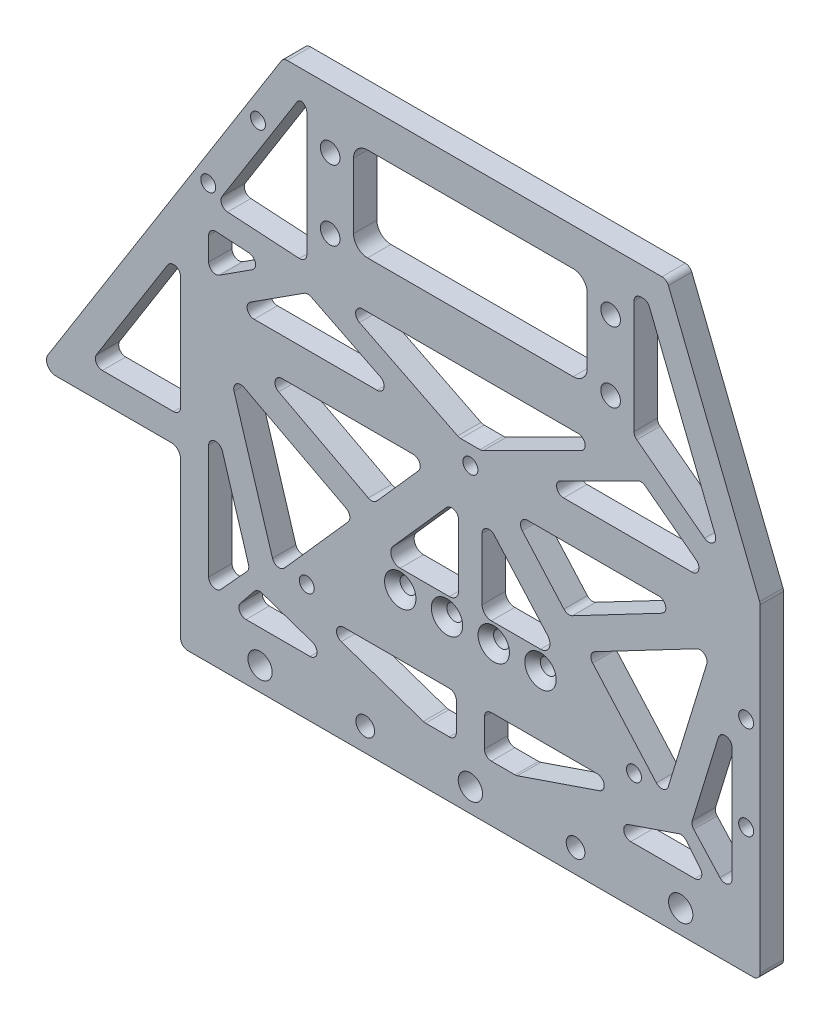
SolidWorks part; units mm, degrees
material "Thornel Mat VMA"
ref_plane "前视基准面" through (0, 0, 0) normal (0, 0, 1) x (1, 0, 0)
ref_plane "上视基准面" through (0, 0, 0) normal (0, 1, 0) x (1, 0, 0)
ref_plane "右视基准面" through (0, 0, 0) normal (1, 0, 0) x (0, 0, -1)
sketch "草图1" plane through (0, 0, 0) normal (0, 0, 1) x (1, 0, 0)
  line L1 (-62, 60) -> (62, 60)
  line L2 (-62, 60) -> (-62, -60)
  line L3 (-62, -60) -> (62, -60)
  line L4 (62, 60) -> (62, -60)
  line L5 (-62, 60) -> (62, -60) construction
  line L6 (-62, -60) -> (62, 60) construction
  point P0 (0, 0)
  dimension "D1" = 124
  dimension "D2" = 120
extrude "凸台-拉伸1" add sketch "草图1" along normal blind 5
sketch "草图2" plane through (0, 0, 5) normal (0, 0, 1) x (1, 0, 0)
  line L0 (-35, -35) -> (35, -35) construction
  line L1 (-62, -60) -> (62, -60) construction
  circle A0 centre (-35, -35) radius 1.6
  circle A1 centre (35, -35) radius 1.6
  point P2 (0, -35)
  dimension "D3" = 3.2
  dimension "D1" = 70
  dimension "D2" = 25
extrude "切除-拉伸1" cut sketch "草图2" against normal through all
sketch "草图3" plane through (0, 0, 5) normal (0, 0, 1) x (1, 0, 0)
  circle A0 centre (0, 4.5) radius 1.6
  circle A1 centre (35, -35) radius 1.6 construction
  dimension "D1" = 3.2
  dimension "D2" = 39.5
extrude "切除-拉伸2" cut sketch "草图3" against normal through all
sketch "草图4" plane through (0, 0, 5) normal (0, 0, 1) x (1, 0, 0)
  line L1 (-30, 47.5) -> (30, 47.5) construction
  line L2 (-30, 47.5) -> (-30, 32.5) construction
  line L3 (-30, 32.5) -> (30, 32.5) construction
  line L4 (30, 47.5) -> (30, 32.5) construction
  line L5 (-30, 47.5) -> (30, 32.5) construction
  line L6 (-30, 32.5) -> (30, 47.5) construction
  circle A0 centre (-30, 47.5) radius 2.1
  circle A1 centre (30, 32.5) radius 2.1
  circle A2 centre (30, 47.5) radius 2.1
  circle A3 centre (-30, 32.5) radius 2.1
  point P0 (0, 40)
  dimension "D4" = 4.2
  dimension "D1" = 40
  dimension "D2" = 15
  dimension "D3" = 60
extrude "切除-拉伸3" cut sketch "草图4" against normal through all
chamfer "倒角1" distance 22 distance2 35 1 edges at (-62, 60, 2.5) first distance on face at (0, 60, 2.5)
chamfer "倒角2" distance 50 distance2 20 1 edges at (62, 60, 2.5) first distance on face at (62, 0, 2.5)
sketch "草图7" plane through (0, 0, 5) normal (0, 0, 1) x (1, 0, 0)
  line L0 (-45, -55) -> (45, -55) construction
  line L1 (-62, -60) -> (62, -60) construction
  circle A0 centre (-45, -55) radius 2.6
  circle A1 centre (0, -55) radius 2.6
  circle A2 centre (45, -55) radius 2.6
  point P4 (0, -55)
  dimension "D3" = 5.2
  dimension "D1" = 5
  dimension "D2" = 90
extrude "切除-拉伸4" cut sketch "草图7" against normal through all
sketch "草图8" plane through (0, 0, 0) normal (0, 0, -1) x (-1, 0, 0)
  circle A0 centre (-59, -33) radius 1.6
  circle A1 centre (-59, -13) radius 1.6
  circle A2 centre (45.4427, 45.7039) radius 1.6
  circle A3 centre (56.0861, 28.7712) radius 1.6
  circle A4 centre (30, 47.5) radius 2.1 construction
  dimension "D1" = 3.2
  dimension "D2" = 45.4427
  dimension "D3" = 56.0861
  dimension "D4" = 59
  dimension "D5" = 28.7712
  dimension "D6" = 45.7039
  dimension "D7" = 13
  dimension "D8" = 33
extrude "切除-拉伸5" cut sketch "草图8" against normal through all
sketch "草图9" plane through (0, 0, 5) normal (0, 0, 1) x (1, 0, 0)
  line L6 (0, 4.5) -> (-35, -35)
  line L7 (25, 52) -> (-25, 52)
  line L8 (25, 52) -> (25, 32)
  line L9 (25, 32) -> (-25, 32)
  line L10 (-25, 52) -> (-25, 32)
  line L11 (25, 52) -> (-25, 32) construction
  line L12 (56, -54) -> (56, 8.8445)
  line L13 (56, 8.8445) -> (37.9378, 54)
  line L14 (37.9378, 54) -> (-36.6846, 54)
  line L15 (-36.6846, 54) -> (-56, 23.2709)
  line L16 (-56, 23.2709) -> (-56, -54)
  line L17 (-56, -54) -> (56, -54)
  line L18 (56, -54) -> (56, 8.8445)
  line L19 (56, 8.8445) -> (37.9378, 54)
  line L20 (37.9378, 54) -> (-36.6846, 54)
  line L21 (-36.6846, 54) -> (-56, 23.2709)
  line L22 (-56, 23.2709) -> (-56, -54)
  line L23 (-56, -54) -> (56, -54)
  line L24 (25, 32) -> (-25, 52) construction
  line L25 (-35, -35) -> (35, -35)
  line L26 (35, -35) -> (0, 4.5)
  line L27 (43.8887, -39) -> (1.8, 8.5)
  line L28 (-1.8, 8.5) -> (-43.8887, -39)
  line L29 (-43.8887, -39) -> (43.8887, -39)
  line L30 (28.3335, -32) -> (0, -0.0236)
  line L31 (0, -0.0236) -> (-28.3335, -32)
  line L32 (-28.3335, -32) -> (28.3335, -32)
  line L33 (56, 4.5) -> (-56, 4.5)
  line L34 (56, 8.5) -> (-56, 8.5)
  line L35 (56, 0.5) -> (-56, 0.5)
  line L36 (43.8887, -39) -> (56, 0.5)
  line L37 (43.8887, -39) -> (56, -54)
  line L38 (-56, 0.5) -> (-43.8887, -39)
  line L39 (-56, -54) -> (-43.8887, -39)
  line L40 (-58.8682, -0.3794) -> (-47.2241, -38.3555)
  line L41 (47.2241, -38.3555) -> (56, -48)
  line L42 (-47.2241, -38.3555) -> (-56, -48)
  line L43 (47.2241, -38.3555) -> (58.8682, -0.3794)
  line L44 (-53.1318, 1.3794) -> (-40.5532, -39.6445)
  line L45 (36.118, 19.7639) -> (39.1448, 21.2773)
  line L46 (-52.8621, 0.5) -> (-22.8444, -15.25)
  line L47 (40.5532, -39.6445) -> (53.1318, 1.3794)
  line L48 (35, 22) -> (-35, 22)
  line L49 (-35, 62) -> (-35, 22)
  line L50 (35, 62) -> (-35, 62)
  line L51 (35, 62) -> (35, 22)
  line L52 (25, 32) -> (56, 8.5)
  line L53 (-35, 22) -> (-56, 23.2709)
  line L54 (-35, 22) -> (-56, 8.5)
  line L55 (-27.2138, 24.0334) -> (-54.6481, 6.3971)
  line L56 (-27.2138, 24.0334) -> (-55.849, 25.7663)
  line L57 (-42.7862, 19.9666) -> (-57.3519, 10.6029)
  line L58 (-42.7862, 19.9666) -> (-56.151, 20.7755)
  line L59 (35, 22) -> (0, 4.5)
  line L60 (-35, 22) -> (0, 4.5)
  line L61 (23.4897, 30.0077) -> (54.4897, 6.5077)
  line L62 (33.882, 24.2361) -> (0, 7.2951)
  line L63 (-33.882, 24.2361) -> (0, 7.2951)
  line L64 (26.5103, 33.9923) -> (57.5103, 10.4923)
  line L65 (36.118, 19.7639) -> (0, 1.7049)
  line L66 (-36.118, 19.7639) -> (0, 1.7049)
  line L67 (0, -0.0236) -> (0, -32)
  line L68 (-2.5, -0.0236) -> (-2.5, -32)
  line L69 (2.5, -0.0236) -> (2.5, -32)
  line L70 (43.8887, -39) -> (0, -54)
  line L71 (0, -54) -> (-43.8887, -39)
  line L72 (43.0801, -36.6344) -> (0, -51.358)
  line L73 (0, -51.358) -> (-43.0801, -36.6344)
  line L74 (52.8621, 0.5) -> (22.8444, -15.25)
  line L75 (51.4683, 3.1565) -> (21.4505, -12.5935)
  line L76 (-56, -48) -> (56, -48)
  line L77 (-54.256, -2.1565) -> (-24.2382, -17.9065)
  line L78 (54.256, -2.1565) -> (24.2382, -17.9065)
  line L79 (-53.6659, -55.8846) -> (-40.5532, -39.6445) construction
  line L80 (40.5532, -39.6445) -> (53.6659, -55.8846) construction
  line L81 (-51.4683, 3.1565) -> (-21.4505, -12.5935)
  line L82 (21.4505, -12.5935) -> (20.7951, -12.9373)
  line L83 (-21.4505, -12.5935) -> (-20.7951, -12.9373)
  line L84 (43.8887, -39) -> (0, 10.5315) construction
  line L85 (0, 10.5315) -> (-43.8887, -39) construction
  line L86 (44.6972, -41.3656) -> (0, -56.642)
  line L87 (0, -56.642) -> (-44.6972, -41.3656)
  line L88 (-44.6972, -41.3656) -> (-45.5605, -41.0706)
  line L89 (44.6972, -41.3656) -> (45.5605, -41.0706)
  line L90 (0, -48) -> (0, -39)
  line L91 (3, -48) -> (3, -39)
  line L92 (-3, -48) -> (-3, -39)
  line L99 (-58.3341, -52.1154) -> (-47.2241, -38.3555) construction
  line L100 (47.2241, -38.3555) -> (58.3341, -52.1154) construction
  point P0 (0, 42)
  dimension "D2" = 42
  dimension "D3" = 20
  dimension "D4" = 50
  dimension "D1" = 6
  dimension "D5" = 4
  dimension "D6" = 3
  dimension "D7" = 4
  dimension "D8" = 4
  dimension "D9" = 3
  dimension "D10" = 3
  dimension "D11" = 10
  dimension "D12" = 2.5
  dimension "D13" = 2.5
  dimension "D14" = 2.5
  dimension "D15" = 2.5
  dimension "D16" = 2.5
  dimension "D17" = 2.5
  dimension "D18" = 2.5
  dimension "D19" = 3
  dimension "D20" = 6
  dimension "D21" = 3
  dimension "D22" = 2.5
  dimension "D23" = 3
  dimension "D24" = 3
extrude "切除-拉伸6" cut sketch "草图9" against normal blind 10 contours L51 L64 L19 L20 | L7 L10 L9 L8 | L56 L49 L20 L21 | L57 L58 L22 | L48 L63 L34 L28 L27 L62 | L45 L65 L34 L61 | L66 L55 L34 | L35 L44 L28 | L27 L47 L35 | L30 L69 L32 | L68 L31 L32 | L22 L76 L40 | L81 L83 L28 L35 | L82 L75 L35 L27 | L76 L92 L29 L73 | L91 L76 L72 L29 | L89 L86 L76 L37 | L87 L88 L39 L76 | L76 L18 L43 region at (-25.363, -3.9791, 5) region at (25.363, -3.9791, 5) region at (34.0343, 12.3435, 5) region at (-33.2707, 12.0425, 5) region at (0, 17.1592, 5) region at (0, 42, 5) region at (53.0747, -32.0298, 5) region at (-51.5954, 17.4017, 5) region at (-53.0747, -32.0298, 5) region at (-41.5375, 35.483, 5) region at (-39.3584, -19.1564, 5) region at (39.3584, -19.1564, 5) region at (40.6672, -45.6902, 5) region at (41.6524, 33.1508, 5) region at (-40.6672, -45.6902, 5) region at (14.4412, -42.5121, 5) region at (-14.4412, -42.5121, 5) region at (11.1112, -22.2817, 5) region at (-11.1112, -22.2817, 5)
fillet "圆角2" radius 1.5 64 edges at (-56, -48, 2.5) (-56, -9.7338, 2.5) (-47.2241, -38.3555, 2.5) (3, -39, 2.5) (36.1585, -39, 2.5) (9.8253, -48, 2.5) (3, -48, 2.5) (20.7951, -12.9373, 2.5) (8.8887, 0.5, 2.5) (46.4052, 0.5, 2.5) (-56, 11.472, 2.5) (-56, 20.7663, 2.5) (-42.7862, 19.9666, 2.5) (2.4098, 8.5, 2.5) (-2.4098, 8.5, 2.5) (-29.4098, 22, 2.5) (29.4098, 22, 2.5) (-13.5902, 8.5, 2.5) (-51.3769, 8.5, 2.5) (-34.8452, 19.1275, 2.5) (56, -9.7338, 2.5) (56, -48, 2.5) (47.2241, -38.3555, 2.5) (37.9378, 54, 2.5) (54.3968, 12.8525, 2.5) (35, 27.5565, 2.5) (35, 54, 2.5) (-40, 60, 2.5) (-62, -60, 2.5) (62, -60, 2.5) (62, 10, 2.5) (42, 60, 2.5) (-51.1555, -48, 2.5) (-45.5605, -41.0706, 2.5) (-25.2857, -48, 2.5) (24.8936, -17.5627, 2.5) (51.6242, -3.5374, 2.5) (41.5575, -36.3691, 2.5) (-24.8936, -17.5627, 2.5) (-41.5575, -36.3691, 2.5) (-51.6242, -3.5374, 2.5) (36.6512, 20.0305, 2.5) (51.8616, 8.5, 2.5) (13.5902, 8.5, 2.5) (-54.4834, 25.6837, 2.5) (-36.6846, 54, 2.5) (-35, 54, 2.5) (-35, 24.5046, 2.5) (-36.1585, -39, 2.5) (-3, -39, 2.5) (-3, -48, 2.5) (-9.8253, -48, 2.5) (45.5605, -41.0706, 2.5) (51.1555, -48, 2.5) (25.2857, -48, 2.5) (2.5, -32, 2.5) (2.5, -2.845, 2.5) (28.3335, -32, 2.5) (-2.5, -32, 2.5) (-28.3335, -32, 2.5) (-2.5, -2.845, 2.5) (-8.8887, 0.5, 2.5) (-20.7951, -12.9373, 2.5) (-46.4052, 0.5, 2.5)
fillet "圆角3" radius 3 4 edges at (25, 32, 2.5) (-25, 52, 2.5) (25, 52, 2.5) (-25, 32, 2.5)
sketch "草图10" plane through (0, 0, 5) normal (0, 0, 1) x (1, 0, 0)
  line L0 (-45, -55) -> (0, -55) construction
  line L1 (0, -55) -> (45, -55) construction
  circle A0 centre (-22.5, -55) radius 2
  circle A1 centre (22.5, -55) radius 2
  dimension "D1" = 4
extrude "切除-拉伸7" cut sketch "草图10" against normal blind 10
sketch "草图11" plane through (0, 0, 5) normal (0, 0, 1) x (1, 0, 0)
  line L0 (-19.4727, -22) -> (19.4727, -22)
  line L1 (26.1229, -29.5052) -> (5.1227, -5.8049) construction
  line L2 (-5.1227, -5.8049) -> (-26.1229, -29.5052) construction
  line L3 (26.1229, -29.5052) -> (5.1227, -5.8049)
  line L4 (4, -32) -> (25.0003, -32)
  line L5 (2.5, -6.7997) -> (2.5, -30.5)
  line L6 (26.1229, -29.5052) -> (5.1227, -5.8049)
  line L7 (4, -32) -> (25.0003, -32)
  line L8 (2.5, -6.7997) -> (2.5, -30.5)
  line L9 (-5.1227, -5.8049) -> (-26.1229, -29.5052)
  line L10 (-2.5, -30.5) -> (-2.5, -6.7997)
  line L11 (-25.0003, -32) -> (-4, -32)
  line L12 (-5.1227, -5.8049) -> (-26.1229, -29.5052)
  line L13 (-2.5, -30.5) -> (-2.5, -6.7997)
  line L14 (-25.0003, -32) -> (-4, -32)
  arc A3 (25.0003, -32) -> (26.1229, -29.5052) centre (25.0003, -30.5) ccw
  arc A4 (2.5, -30.5) -> (4, -32) centre (4, -30.5) ccw
  arc A5 (5.1227, -5.8049) -> (2.5, -6.7997) centre (4, -6.7997) ccw
  arc A6 (25.0003, -32) -> (26.1229, -29.5052) centre (25.0003, -30.5) ccw
  arc A7 (2.5, -30.5) -> (4, -32) centre (4, -30.5) ccw
  arc A8 (5.1227, -5.8049) -> (2.5, -6.7997) centre (4, -6.7997) ccw
  arc A9 (-2.5, -6.7997) -> (-5.1227, -5.8049) centre (-4, -6.7997) ccw
  arc A10 (-4, -32) -> (-2.5, -30.5) centre (-4, -30.5) ccw
  arc A11 (-26.1229, -29.5052) -> (-25.0003, -32) centre (-25.0003, -30.5) ccw
  arc A12 (-2.5, -6.7997) -> (-5.1227, -5.8049) centre (-4, -6.7997) ccw
  arc A13 (-4, -32) -> (-2.5, -30.5) centre (-4, -30.5) ccw
  arc A14 (-26.1229, -29.5052) -> (-25.0003, -32) centre (-25.0003, -30.5) ccw
  point P19 (19.4727, -22)
  point P23 (-19.4727, -22)
  dimension "D3" = 10
  dimension "D1" = 0
  dimension "D2" = 0
extrude "凸台-拉伸2" add sketch "草图11" against normal up to surface (5 mm away) contours L12 A14 L14 A13 L13 L0 | L8 A7 L7 A6 L6 L0 region at (13.2233, -27.2892, 5) region at (-13.2233, -27.2892, 5) up to face at (-20.5, -55, 0)
fillet "圆角4" radius 2 4 edges at (19.4727, -22, 2.5) (-19.4727, -22, 2.5) (-2.5, -22, 2.5) (2.5, -22, 2.5)
sketch "草图12" plane through (0, 0, 5) normal (0, 0, 1) x (1, 0, 0)
  line L0 (-15, -26) -> (15, -26) construction
  line L1 (0, 0) -> (0, -26) construction
  line L2 (4.5, -22) -> (15.0284, -22) construction
  circle A0 centre (-15, -26) radius 1.55
  circle A1 centre (-5, -26) radius 1.55
  circle A2 centre (5, -26) radius 1.55
  circle A3 centre (15, -26) radius 1.55
  point P8 (0, 0)
  dimension "D3" = 3.1
  dimension "D1" = 30
  dimension "D2" = 4
  dimension "D4" = 4
extrude "切除-拉伸8" cut sketch "草图12" against normal through all
hole_wizard "M3 六角凹锥坑螺钉的锥形沉头孔1" positions "草图13" profile "草图14" countersink size "M3" standard "ISO" end condition up to next
sketch "草图13" plane through (0, 0, 5) normal (0, 0, 1) x (1, 0, 0)
  point P0 (-15, -26)
  point P3 (-5, -26)
  point P6 (5, -26)
  point P9 (15, -26)
sketch "草图14" plane through (-15, -26, 5) normal (1, 0, 0) x (0, -1, 0)
  line L0 (0, 0) -> (0, 5)
  line L1 (0, 5) -> (1.7, 5)
  line L2 (1.7, 5) -> (1.7, 1.66)
  line L3 (1.7, 1.66) -> (3.36, 0)
  line L5 (3.36, 0) -> (0, 0)
  line L6 (-1.7, 1.66) -> (-3.36, 0) construction
  line L11 (0, -6.35) -> (0, 107.95) construction
  dimension "通孔孔直径" = 3.4
  dimension "通孔孔深度" = 5
  dimension "近端锥形沉头孔直径" = 6.72
  dimension "近端锥形沉头孔角度" = 90
sketch "草图15" plane through (0, 0, 5) normal (0, 0, 1) x (1, 0, 0)
  line L5 (-62, 25) -> (-92.3152, -23.2288)
  line L6 (-92.3152, -23.2288) -> (-62, -23.2288)
  line L8 (-62, -23.2288) -> (-62, 25)
  line L9 (-40.4411, 59.2983) -> (-62, 25) construction
  circle A0 centre (-56.0861, 28.7712) radius 1.6 construction
  point P2 (-62, 25)
  point P3 (-80.3743, -4.2318)
  dimension "D1" = 52
extrude "凸台-拉伸3" add sketch "草图15" against normal up to surface (5 mm away) up to face at (-13.3, -26, 0)
fillet "圆角5" radius 2 2 edges at (-92.3152, -23.2288, 2.5) (-62, -23.2288, 2.5)
sketch "草图16" plane through (0, 0, 5) normal (0, 0, 1) x (1, 0, 0)
  line L0 (-62, 13.7254) -> (-81.4569, -17.2288)
  line L1 (-81.4569, -17.2288) -> (-62, -17.2288)
  line L2 (-62, -17.2288) -> (-62, 13.7254)
  line L4 (-62, -25.2288) -> (-62, -58.5) construction
  line L5 (-88.6958, -23.2288) -> (-64, -23.2288) construction
  line L6 (-37.1257, 53.2983) -> (-53.1366, 27.8263) construction
  point P11 (-69.1972, -12.3835)
  dimension "D1" = 6
extrude "切除-拉伸9" cut sketch "草图16" against normal blind 10
fillet "圆角6" radius 1.5 3 edges at (-62, 13.7254, 2.5) (-62, -17.2288, 2.5) (-81.4569, -17.2288, 2.5)
